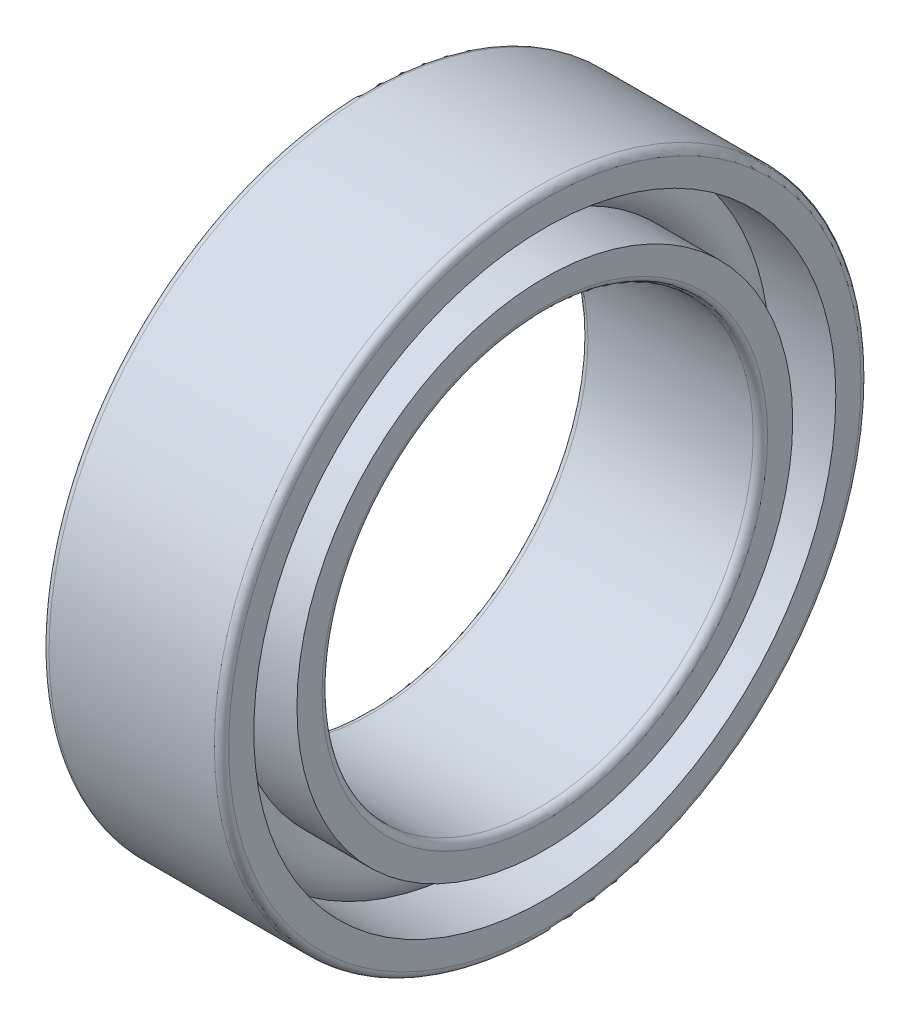
SolidWorks part; units mm, degrees
ref_plane "Plane1" through (0, 0, 0) normal (0, 0, 1) x (1, 0, 0)
ref_plane "Plane2" through (0, 0, 0) normal (0, 1, 0) x (1, 0, 0)
ref_plane "Plane3" through (0, 0, 0) normal (1, 0, 0) x (0, 0, -1)
other "Configuration Table"
sketch "Clipboard" plane through (0, 0, 0) normal (0, 0, 1) x (1, 0, 0)
  line L0 (-10, 0) -> (10, 0) construction
  line L1 (0, 0) -> (22.3471, -0.7804)
  line L2 (0, 0) -> (7.4954, 0.2617)
  line L3 (0, 0) -> (22.3471, -0.7804)
  line L4 (0, 0) -> (-22.3573, -0.3902)
  dimension "BallCLRad" = 7.5
  dimension "Count" = 2
sketch "CagSpiSke" plane through (0, 0, 0) normal (0, 0, 1) x (1, 0, 0)
  line L0 (0.09, 7.35) -> (0.09, 7.65)
  line L1 (0.09, 7.65) -> (-0.09, 7.65)
  line L2 (-0.09, 7.65) -> (-0.09, 7.35)
  line L3 (-0.09, 7.35) -> (0.09, 7.35)
  line L4 (-20.6375, 0) -> (20.6375, 0) construction
  line L5 (0, 0) -> (0, 23.7692) construction
  dimension "OD" = 15.3
  dimension "ID" = 14.7
revolve "CageSpine" add sketch "CagSpiSke" angle 0.001 about L4 reverse direction yes
ref_axis "Axis1" through (-50, 0, 0) along (1, 0, 0)
sketch "CagBalSke" plane through (0, 0, 0) normal (0, 0, 1) x (1, 0, 0)
  line L0 (-0.99, 7.5) -> (0.99, 7.5)
  line L1 (-1.905, 7.5) -> (1.905, 7.5) construction
  line L2 (-10, 0) -> (10, 0) construction
  line L3 (0, 0) -> (0, 24) construction
  arc A0 (0.99, 7.5) -> (-0.99, 7.5) centre (0, 7.5) cw
  dimension "BallCLRad" = 7.5
revolve "CageBall" [suppressed] add sketch "CagBalSke" angle 360 about L1 reverse direction yes
pattern_circular "CageBalls" [suppressed] count 2 every 180 about axis through (-50, 0, 0) along (1, 0, 0)
sketch "CagTrmODSke" plane through (0, 0, 0) normal (0, 0, 1) x (1, 0, 0)
  line L0 (0.991, 7.65) -> (0.991, 8.491)
  line L1 (0.991, 8.491) -> (-0.991, 8.491)
  line L2 (-0.991, 8.491) -> (-0.991, 7.65)
  line L3 (-0.991, 7.65) -> (0.991, 7.65)
  line L4 (-20.6375, 0) -> (20.6375, 0) construction
  line L5 (0, 0) -> (0, 25) construction
  dimension "Width" = 1.982
  dimension "ID" = 15.3
  dimension "OD" = 16.982
revolve "CageTrimOD" [suppressed] cut sketch "CagTrmODSke" angle 360 about L4 reverse direction yes
sketch "CagTrmIDSke" plane through (0, 0, 0) normal (0, 0, 1) x (1, 0, 0)
  line L0 (0.991, 6.511) -> (0.991, 7.35)
  line L1 (0.991, 7.35) -> (-0.991, 7.35)
  line L2 (-0.991, 7.35) -> (-0.991, 6.511)
  line L3 (-0.991, 6.511) -> (0.991, 6.511)
  line L4 (-20.6375, 0) -> (20.6375, 0) construction
  line L5 (0, 0) -> (0, 25) construction
  dimension "Width" = 1.982
  dimension "ID" = 13.022
  dimension "OD" = 14.7
revolve "CageTrimID" [suppressed] cut sketch "CagTrmIDSke" angle 360 about L4 reverse direction yes
sketch "BalSimSke" plane through (0, 0, 0) normal (0, 0, 1) x (1, 0, 0)
  line L0 (-10, 0) -> (10, 0) construction
  line L1 (-10, 7.5) -> (10, 7.5) construction
  line L2 (0, 0) -> (0, 23) construction
  circle A0 centre (0, 7.5) radius 0.9
  dimension "BallCLRad" = 7.5
revolve "BallsSimplified" add sketch "BalSimSke" angle 360 about L0
sketch "BalDetSke" plane through (0, 0, 0) normal (0, 0, 1) x (1, 0, 0)
  line L0 (-0.9, 7.5) -> (0.9, 7.5)
  line L1 (-1.905, 7.5) -> (1.905, 7.5) construction
  line L2 (0, 0) -> (0, 25) construction
  arc A0 (0.9, 7.5) -> (-0.9, 7.5) centre (0, 7.5) cw
  dimension "BallCLRad" = 7.5
revolve "BallDetailed" [suppressed] add sketch "BalDetSke" angle 360 about L1 reverse direction yes
sketch "InnRacSke" plane through (0, 0, 0) normal (0, 0, 1) x (1, 0, 0)
  line L0 (-0.6369, 6.9) -> (-2.5, 6.9)
  line L1 (-2.5, 6.9) -> (-2.5, 6.2)
  line L2 (-2.3, 6) -> (2.3, 6)
  line L3 (2.5, 6.2) -> (2.5, 6.9)
  line L4 (2.5, 6.9) -> (0.6369, 6.9)
  line L5 (-20.6375, 0) -> (20.6375, 0) construction
  line L6 (0, 0) -> (0, 30) construction
  arc A0 (-2.5, 6.2) -> (-2.3, 6) centre (-2.3, 6.2) ccw
  arc A1 (2.3, 6) -> (2.5, 6.2) centre (2.3, 6.2) ccw
  arc A2 (0.6369, 6.9) -> (-0.6369, 6.9) centre (0, 7.5) cw
  dimension "BallCLRad" = 7.5
  dimension "Fillet_radius" = 0.2
  dimension "Ball_diameter" = 1.75
  dimension "ID" = 12
  dimension "OD" = 13.8
  dimension "Width" = 5
revolve "InnerRace" add sketch "InnRacSke" angle 360 about L5 reverse direction yes
sketch "OutRacSke" plane through (0, 0, 0) normal (0, 0, 1) x (1, 0, 0)
  line L0 (-0.6369, 8.1) -> (-2.5, 8.1)
  line L1 (-2.5, 8.1) -> (-2.5, 8.8)
  line L2 (-2.3, 9) -> (2.3, 9)
  line L3 (2.5, 8.8) -> (2.5, 8.1)
  line L4 (2.5, 8.1) -> (0.6369, 8.1)
  line L5 (-20.6375, 0) -> (20.6375, 0) construction
  line L6 (0, 0) -> (0, 30) construction
  arc A0 (-2.5, 8.8) -> (-2.3, 9) centre (-2.3, 8.8) cw
  arc A1 (2.3, 9) -> (2.5, 8.8) centre (2.3, 8.8) cw
  arc A2 (0.6369, 8.1) -> (-0.6369, 8.1) centre (0, 7.5) ccw
  dimension "BallCLRad" = 7.5
  dimension "Fillet_radius" = 0.2
  dimension "Ball_diameter" = 1.75
  dimension "Width" = 5
revolve "OuterRace" add sketch "OutRacSke" angle 360 about L5 reverse direction yes
pattern_circular "BallsDetailed" [suppressed] count 2 every 180 about axis through (-50, 0, 0) along (1, 0, 0)
equation "\"BallCLRad@Clipboard\" = ( \"OD@OutRacSke\" + \"ID@InnRacSke\" ) / 4"
equation "\"BallCLRad@BalSimSke\" = \"BallCLRad@Clipboard\""
equation "\"BallCLRad@BalDetSke\" = \"BallCLRad@Clipboard\""
equation "\"BallCLRad@InnRacSke\" = \"BallCLRad@Clipboard\""
equation "\"BallCLRad@OutRacSke\" = \"BallCLRad@Clipboard\""
equation "\"Ball_diameter@InnRacSke\" = \"Ball_diameter@BalDetSke\" - 0.05"
equation "\"Ball_diameter@OutRacSke\" = \"Ball_diameter@BalDetSke\" - 0.05"
equation "\"Ball_diameter@BalSimSke\" = \"Ball_diameter@BalDetSke\""
equation "\"Width@OutRacSke\" = \"Width@InnRacSke\""
equation "\"Fillet_radius@OutRacSke\" = \"Fillet_radius@InnRacSke\""
equation "\"Max_count@Clipboard\" = int( 3.14159265 / atn(( \"Ball_diameter@BalDetSke\" / 2) / sqr( \"BallCLRad@Clipboard\"  *  \"BallCLRad@Clipboard\" - ( \"Ball_diameter@BalDetSke\" / 2) *  ( \"Ball_diameter@BalDetSke\" / 2))))"
equation "\"Max_count@Clipboard\" = ((sgn( \"Max_count@Clipboard\" - \"Count@Clipboard\" )-1)*( \"Max_count@Clipboard\" - \"Count@Clipboard\" ))/-2+ \"Count@Clipboard\""
equation "\"Count@BallsDetailed\" = int( \"Show_count@Clipboard\" ) "
equation "\"Count@BallsDetailed\" = ((sgn( \"Count@BallsDetailed\" - \"Max_count@Clipboard\" )-1)*( \"Count@BallsDetailed\" - \"Max_count@Clipboard\" ))/-2+ \"Max_count@Clipboard\""
equation "\"Count@BallsDetailed\" = ((sgn( \"Count@BallsDetailed\" - \"Min_count@Clipboard\" )+1)*( \"Count@BallsDetailed\" - \"Min_count@Clipboard\"))/2 +\"Min_count@Clipboard\""
equation "\"Angle@BallsDetailed\" = 360.0 / \"Max_count@Clipboard\""
equation "\"BallCLRad@CagBalSke\" = \"BallCLRad@Clipboard\""
equation "\"Count@CageBalls\" = \"Count@BallsDetailed\""
equation "\"Angle@CageBalls\" = \"Angle@BallsDetailed\""
equation "\"Angle@CageSpine\" =  \"Angle@CageBalls\" * ( \"Count@CageBalls\" -1 + int( \"Count@CageBalls\" / \"Max_count@Clipboard\" ) )  + 0.001 -  int( \"Count@CageBalls\" / \"Max_count@Clipboard\" ) * 0.001"
equation "\"Angle@CageSpine\" =  \"Angle@CageSpine\" * int( \"Min_count@Clipboard\" / 2) + int(1 / \"Min_count@Clipboard\")  * 0.001"
equation "\"CageWallOD@CagBalSke\" =  \"Ball_diameter@BalDetSke\" * 1.1"
equation "\"Thickness@CagSpiSke\" =  \"Ball_diameter@BalDetSke\" * 0.1"
equation "\"OD@CagTrmODSke\" = \"BallCLRad@Clipboard\" * 2 + \"CageWallOD@CagBalSke\" + 0.002"
equation "\"ID@CagTrmODSke\" = \"BallCLRad@Clipboard\" * 2 + \"Ball_diameter@BalDetSke\" / 6"
equation "\"OD@CagTrmIDSke\" = \"BallCLRad@Clipboard\" * 2 - \"Ball_diameter@BalDetSke\" / 6"
equation "\"ID@CagTrmIDSke\" = \"BallCLRad@Clipboard\" * 2 - \"CageWallOD@CagBalSke\" + 0.002"
equation "\"OD@CagSpiSke\" = \"ID@CagTrmODSke\""
equation "\"ID@CagSpiSke\" = \"OD@CagTrmIDSke\""
equation "\"Width@CagTrmODSke\" = \"CageWallOD@CagBalSke\" + 0.002"
equation "\"Width@CagTrmIDSke\" = \"CageWallOD@CagBalSke\" + 0.002"
